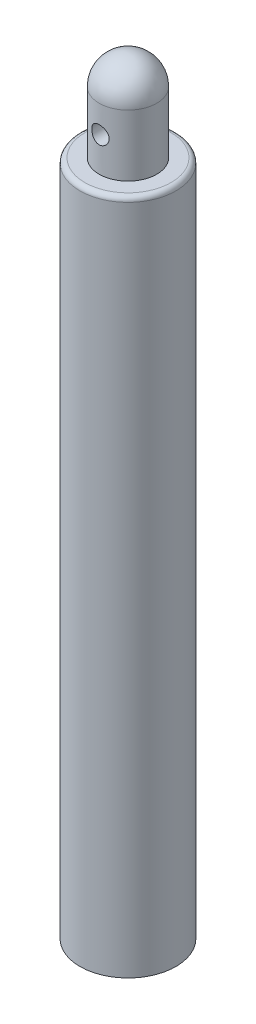
SolidWorks part; units mm, degrees
ref_plane "Front Plane" through (0, 0, 0) normal (0, 0, 1) x (1, 0, 0)
ref_plane "Top Plane" through (0, 0, 0) normal (0, 1, 0) x (1, 0, 0)
ref_plane "Right Plane" through (0, 0, 0) normal (1, 0, 0) x (0, 0, -1)
sketch "Sketch2" plane through (0, 0, 0) normal (0, 1, 0) x (1, 0, 0)
  circle A0 centre (0, 0) radius 4.955
  dimension "D1" = 9.91
extrude "Bottom of Mount" add sketch "Sketch2" along normal blind 69.85
sketch "Sketch3" plane through (0, 69.85, 0) normal (0, 1, 0) x (1, 0, 0)
  circle A0 centre (0, 0) radius 2.975
  dimension "D1" = 5.95
extrude "Top of Mount" add sketch "Sketch3" along normal blind 6.35
sketch "Sketch4" plane through (0, 0, 0) normal (0, -1, 0) x (1, 0, 0)
  circle A0 centre (0, 0) radius 1
  dimension "D1" = 2
extrude "Screw Cut in Bottom" cut sketch "Sketch4" against normal blind 20
sketch "Sketch6" plane through (0, 0, 0) normal (0, 0, 1) x (1, 0, 0)
  line L0 (4.955, 69.85) -> (-4.955, 69.85) construction
  circle A0 centre (0, 73.39) radius 0.9
  dimension "D1" = 1.8
  dimension "D2" = 3.54
extrude "Lock in hole" cut sketch "Sketch6" against normal through all both and the other way through all
sketch "Sketch9" plane through (0, 0, 0) normal (0, 0, 1) x (1, 0, 0)
  line L0 (0, 74.29) -> (0, 72.49) construction
  line L1 (2.975, 76.2) -> (-2.975, 76.2) construction
  line L2 (2.975, 76.2) -> (-2.975, 76.2)
  circle A0 centre (0, 73.39) radius 0.9 construction
  arc A1 (2.975, 76.2) -> (-2.975, 76.2) centre (0, 76.2) ccw
  dimension "D1" = 2.975
revolve "Circular Top" add sketch "Sketch9" angle 360 about L2
fillet "Fillet5" radius 0.5 1 edges at (0, 69.85, 4.955)
